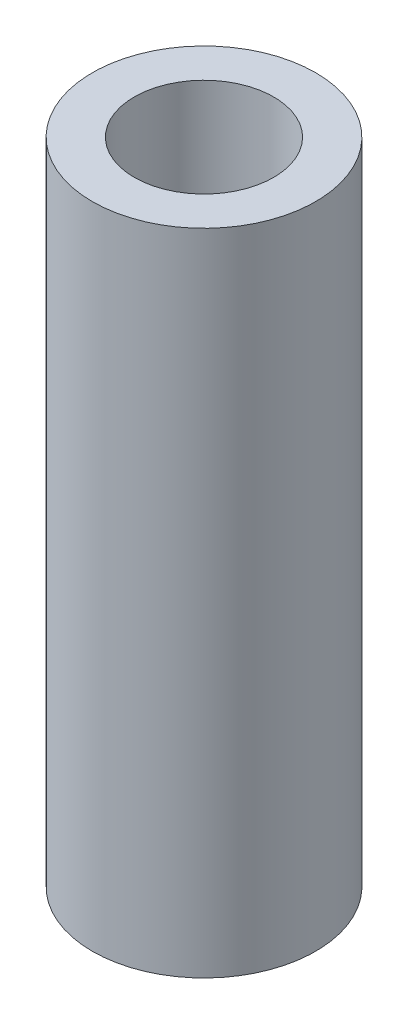
SolidWorks part; units mm, degrees
ref_plane "Front Plane" through (0, 0, 0) normal (0, 0, 1) x (1, 0, 0)
ref_plane "Top Plane" through (0, 0, 0) normal (0, 1, 0) x (1, 0, 0)
ref_plane "Right Plane" through (0, 0, 0) normal (1, 0, 0) x (0, 0, -1)
sketch "Sketch1" plane through (0, 0, 0) normal (0, 1, 0) x (1, 0, 0)
  circle A0 centre (0, 0) radius 15
  dimension "SLEEVE_OD" = 30
extrude "Boss-Extrude1" add sketch "Sketch1" along normal blind 87.2172
sketch "Sketch2" plane through (0, 0, 0) normal (0, 1, 0) x (1, 0, 0)
  circle A0 centre (0, 0) radius 9.3667
  dimension "BORE_D" = 18.7334
extrude "Cut-Extrude1" cut sketch "Sketch2" along normal through all
chamfer "Chamfer1" distance 2.9135 angle 45 rebuild error yes
